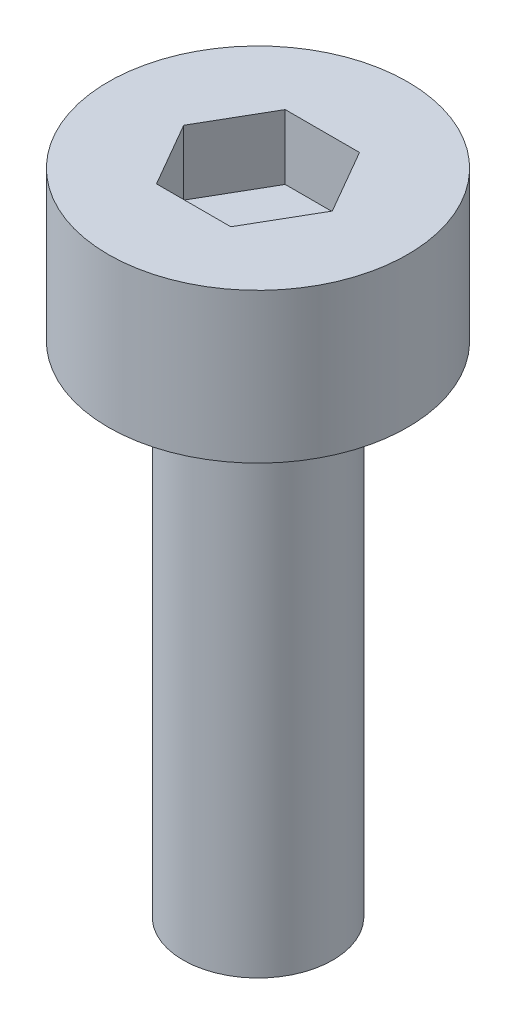
SolidWorks part; units mm, degrees
ref_plane "Front Plane" through (0, 0, 0) normal (0, 0, 1) x (1, 0, 0)
ref_plane "Top Plane" through (0, 0, 0) normal (0, 1, 0) x (1, 0, 0)
ref_plane "Right Plane" through (0, 0, 0) normal (1, 0, 0) x (0, 0, -1)
sketch "Sketch1" plane through (0, 0, 0) normal (0, 1, 0) x (1, 0, 0)
  circle A0 centre (0, 0) radius 1.5
  dimension "D1" = 3
extrude "ScrewShaft" add sketch "Sketch1" along normal blind 10
sketch "Sketch2" plane through (0, 10, 0) normal (0, 1, 0) x (1, 0, 0)
  circle A0 centre (0, 0) radius 3
  dimension "D1" = 6
extrude "Boss-Extrude2" add sketch "Sketch2" along normal blind 3
sketch "Sketch3" plane through (0, 13, 0) normal (0, 1, 0) x (1, 0, 0)
  line L0 (0, 0) -> (0, 1.29) construction
  line L1 (1.4896, 0) -> (0.7448, 1.29)
  line L2 (0.7448, 1.29) -> (-0.7448, 1.29)
  line L3 (-0.7448, 1.29) -> (-1.4896, 0)
  line L4 (-1.4896, 0) -> (-0.7448, -1.29)
  line L5 (-0.7448, -1.29) -> (0.7448, -1.29)
  line L6 (0.7448, -1.29) -> (1.4896, 0)
  circle A0 centre (0, 0) radius 1.29 construction
  dimension "D1" = 2.58
extrude "Cut-Extrude1" cut sketch "Sketch3" against normal blind 1.3
equation "\"X-ROD-SPACING\"=45"
equation "\"Y-ROD-SPACING\"=75"
equation "\"Z-ROD-SPACING\"=17.5"
equation "\"Y-BED-OFFSET\"=2"
equation "\"Y-BED-ROD-INSET\"=3.5"
equation "\"T-SLOT-NUT-FILLET-RADIUS\"=0.25"
equation "\"T-SLOT-SCREW-SHAFT-RADIUS\"=1.75"
equation "\"T-SLOT-SCREW-SHAFT-CUTOUT-LENGTH\"=10.5"
equation "\"T-SLOT-NUT-DEPTH\"=4.2"
equation "\"T-SLOT-NUT-WIDTH\"=3"
equation "\"T-SLOT-NUT-END-DISTANCE\"=8"
equation "\"ACRYLIC-THICKNESS\"=10"
equation "\"ACRYLIC-THICKNESS2\"=4.5"
equation "\"ACRYLIC-TAB-CUTOUT-SIZE\"=\"ACRYLIC-THICKNESS\"+\"ACRYLIC-TAB-TOLERANCE\"*2"
equation "\"ACRYLIC-TAB-WIDTH\"=\"ACRYLIC-THICKNESS\""
equation "\"ACRYLIC-M3-HOLE\"=3.1"
equation "\"SMOOTHROD-CAP-SCREW-DISTANCE\"=20"
equation "\"FRAME-WIDTH-INNER\"=370"
equation "\"NEMA17-HOLE-SPACING\"=31"
equation "\"NEMA17-CENTRAL-CUTOUT\"=22.5"
equation "\"Z-BRACKET-REACH\"=55"
equation "\"TOP-BRACKET-SPACING\"=40"
equation "\"SMOOTHROD-X-LENGTH\"=350"
equation "\"SMOOTHROD-Y-LENGTH\"=350"
equation "\"SMOOTHROD-Z-LENGTH\"=350"
equation "\"SMOOTHROD-TIGHTENING-HEADROOM\"=1"
equation "\"LEADSCREW-Z-LENGTH\"=300"
equation "\"SCREW-LENGTH-FRAME\"=\"ACRYLIC-THICKNESS\" + 10"
equation "\"SCREW-HEAD-RADIUS\"=6"
equation "\"PRINTED-X-SMOOTHROD-DIAMETER\"=8.2"
equation "\"PRINTED-X-SMOOTHROD-CUTOUT\"=10"
equation "\"PRINTED-X-BASE-HEIGHT\"=10"
equation "\"PRINTED-LM8UU-CUTOUT-SIZE\"=15.25"
equation "\"PRINTED-LM8UU-CUTOUT-LENGTH\"=24.5"
equation "\"PRINTED-X-IDLER-HEIGHT\"=16"
equation "\"PSU-MOUNTING-WIDTH\"=95"
equation "\"PSU-MOUNTING-HEIGHT\"=177"
equation "\"D1@Sketch2\"=\"SCREW-HEAD-RADIUS\""
